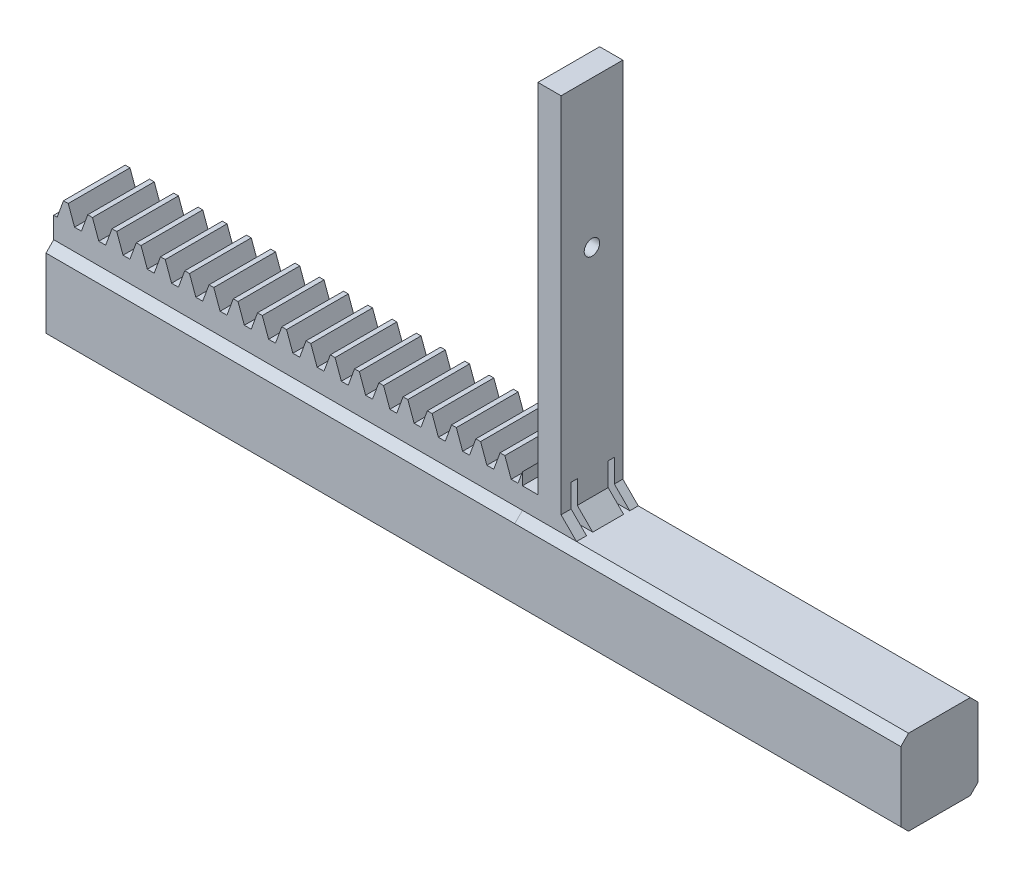
SolidWorks part; units mm, degrees
ref_plane "Front Plane" through (0, 0, 0) normal (0, 0, 1) x (1, 0, 0)
ref_plane "Top Plane" through (0, 0, 0) normal (0, 1, 0) x (1, 0, 0)
ref_plane "Right Plane" through (0, 0, 0) normal (1, 0, 0) x (0, 0, -1)
ref_plane "Plane1" through (0, 0, -3.7928) normal (0, 0, -1) x (-1, 0, 0)
sketch "Sketch1" plane through (0, 0, -3.7928) normal (0, 0, -1) x (-1, 0, 0)
  line L0 (23.517, -6.4086) -> (22.698, -8.6586)
  line L1 (22.698, -8.6586) -> (21.8092, -8.6586)
  line L2 (21.8092, -8.6586) -> (21.2359, -7.0836)
  line L3 (21.2359, -7.0836) -> (21.2359, -12.4086)
  line L4 (21.2359, -12.4086) -> (66.2359, -12.4086)
  line L5 (81.9439, -8.6586) -> (81.9439, -12.4086)
  line L6 (66.6803, -8.6586) -> (65.7915, -8.6586)
  line L7 (65.7915, -8.6586) -> (64.9725, -6.4086)
  line L8 (64.9725, -6.4086) -> (64.3577, -6.4086)
  line L9 (64.3577, -6.4086) -> (63.5387, -8.6586)
  line L10 (63.5387, -8.6586) -> (62.6499, -8.6586)
  line L11 (62.6499, -8.6586) -> (61.8309, -6.4086)
  line L12 (61.8309, -6.4086) -> (61.2161, -6.4086)
  line L13 (61.2161, -6.4086) -> (60.3971, -8.6586)
  line L14 (60.3971, -8.6586) -> (59.5083, -8.6586)
  line L15 (59.5083, -8.6586) -> (58.6893, -6.4086)
  line L16 (58.6893, -6.4086) -> (58.0745, -6.4086)
  line L17 (58.0745, -6.4086) -> (57.2555, -8.6586)
  line L18 (57.2555, -8.6586) -> (56.3667, -8.6586)
  line L19 (56.3667, -8.6586) -> (55.5477, -6.4086)
  line L20 (55.5477, -6.4086) -> (54.9329, -6.4086)
  line L21 (54.9329, -6.4086) -> (54.114, -8.6586)
  line L22 (54.114, -8.6586) -> (53.2251, -8.6586)
  line L23 (53.2251, -8.6586) -> (52.4062, -6.4086)
  line L24 (52.4062, -6.4086) -> (51.7913, -6.4086)
  line L25 (51.7913, -6.4086) -> (50.9724, -8.6586)
  line L26 (50.9724, -8.6586) -> (50.0835, -8.6586)
  line L27 (50.0835, -8.6586) -> (49.2646, -6.4086)
  line L28 (49.2646, -6.4086) -> (48.6497, -6.4086)
  line L29 (48.6497, -6.4086) -> (47.8308, -8.6586)
  line L30 (47.8308, -8.6586) -> (46.9419, -8.6586)
  line L31 (46.9419, -8.6586) -> (46.123, -6.4086)
  line L32 (46.123, -6.4086) -> (45.5081, -6.4086)
  line L33 (45.5081, -6.4086) -> (44.6892, -8.6586)
  line L34 (44.6892, -8.6586) -> (43.8003, -8.6586)
  line L35 (43.8003, -8.6586) -> (42.9814, -6.4086)
  line L36 (42.9814, -6.4086) -> (42.3665, -6.4086)
  line L37 (42.3665, -6.4086) -> (41.5476, -8.6586)
  line L38 (41.5476, -8.6586) -> (40.6587, -8.6586)
  line L39 (40.6587, -8.6586) -> (39.8398, -6.4086)
  line L40 (39.8398, -6.4086) -> (39.2249, -6.4086)
  line L41 (39.2249, -6.4086) -> (38.406, -8.6586)
  line L42 (38.406, -8.6586) -> (37.5171, -8.6586)
  line L43 (37.5171, -8.6586) -> (36.6982, -6.4086)
  line L44 (36.6982, -6.4086) -> (36.0833, -6.4086)
  line L45 (36.0833, -6.4086) -> (35.2644, -8.6586)
  line L46 (35.2644, -8.6586) -> (34.3755, -8.6586)
  line L47 (34.3755, -8.6586) -> (33.5566, -6.4086)
  line L48 (33.5566, -6.4086) -> (32.9417, -6.4086)
  line L49 (32.9417, -6.4086) -> (32.1228, -8.6586)
  line L50 (32.1228, -8.6586) -> (31.2339, -8.6586)
  line L51 (31.2339, -8.6586) -> (30.415, -6.4086)
  line L52 (30.415, -6.4086) -> (29.8001, -6.4086)
  line L53 (29.8001, -6.4086) -> (28.9812, -8.6586)
  line L54 (28.9812, -8.6586) -> (28.0923, -8.6586)
  line L55 (28.0923, -8.6586) -> (27.2734, -6.4086)
  line L56 (27.2734, -6.4086) -> (26.6586, -6.4086)
  line L57 (26.6586, -6.4086) -> (25.8396, -8.6586)
  line L58 (25.8396, -8.6586) -> (24.9508, -8.6586)
  line L59 (24.9508, -8.6586) -> (24.1318, -6.4086)
  line L60 (24.1318, -6.4086) -> (23.517, -6.4086)
  line L61 (81.4994, -8.6586) -> (81.9439, -8.6586)
  line L62 (80.6805, -6.4086) -> (81.4994, -8.6586)
  line L63 (80.0656, -6.4086) -> (80.6805, -6.4086)
  line L64 (79.2467, -8.6586) -> (80.0656, -6.4086)
  line L65 (78.3578, -8.6586) -> (79.2467, -8.6586)
  line L66 (77.5389, -6.4086) -> (78.3578, -8.6586)
  line L67 (76.924, -6.4086) -> (77.5389, -6.4086)
  line L68 (76.1051, -8.6586) -> (76.924, -6.4086)
  line L69 (75.2162, -8.6586) -> (76.1051, -8.6586)
  line L70 (74.3973, -6.4086) -> (75.2162, -8.6586)
  line L71 (73.7824, -6.4086) -> (74.3973, -6.4086)
  line L72 (72.9635, -8.6586) -> (73.7824, -6.4086)
  line L73 (72.0746, -8.6586) -> (72.9635, -8.6586)
  line L74 (71.2557, -6.4086) -> (72.0746, -8.6586)
  line L75 (70.6409, -6.4086) -> (71.2557, -6.4086)
  line L76 (69.8219, -8.6586) -> (70.6409, -6.4086)
  line L77 (68.933, -8.6586) -> (69.8219, -8.6586)
  line L78 (68.1141, -6.4086) -> (68.933, -8.6586)
  line L79 (67.4993, -6.4086) -> (68.1141, -6.4086)
  line L80 (66.6803, -8.6586) -> (67.4993, -6.4086)
  line L81 (66.2359, -12.4086) -> (81.9439, -12.4086)
extrude "Boss-Extrude1" add sketch "Sketch1" against normal blind 8
sketch "Sketch2" plane through (0, -12.4086, 0) normal (0, -1, 0) x (1, 0, 0)
  line L0 (-81.9439, 4.2072) -> (-81.9439, -3.7928) construction
  line L1 (-81.9439, 5.2072) -> (28.7641, 5.2072)
  line L2 (-81.9439, 5.2072) -> (-81.9439, -4.7928)
  line L3 (-81.9439, -4.7928) -> (28.7641, -4.7928)
  line L4 (28.7641, 5.2072) -> (28.7641, -4.7928)
  line L5 (-21.2359, 4.2072) -> (-21.2359, -3.7928) construction
  point P8 (-81.9439, 0.2072)
  dimension "D1" = 10
  dimension "D2" = 50
extrude "Boss-Extrude2" add sketch "Sketch2" along normal blind 10
chamfer "Chamfer1" distance 1 angle 45 1 edges at (-51.5899, -12.4086, 4.2072)
chamfer "Chamfer2" distance 1 angle 45 1 edges at (-51.5899, -12.4086, -3.7928)
sketch "Sketch3" plane through (0, -12.4086, 0) normal (0, 1, 0) x (1, 0, 0)
  line L1 (-21.2359, 3.7928) -> (28.7641, 3.7928)
  line L2 (-21.2359, 3.7928) -> (-21.2359, -4.2072)
  line L3 (-21.2359, -4.2072) -> (28.7641, -4.2072)
  line L4 (28.7641, 3.7928) -> (28.7641, -4.2072)
  line L6 (28.7641, 4.7928) -> (28.7641, -5.2072) construction
  dimension "D1" = 8
extrude "Boss-Extrude3" add sketch "Sketch3" along normal blind 1
chamfer "Chamfer3" distance 1 angle 45 1 edges at (3.7641, -12.4086, 4.2072)
chamfer "Chamfer4" distance 1 angle 45 1 edges at (3.7641, -12.4086, -3.7928)
sketch "Sketch4" plane through (0, -22.4086, 0) normal (0, -1, 0) x (1, 0, 0)
  line L1 (-19.2359, 4.2072) -> (-16.2359, 4.2072)
  line L2 (-19.2359, 4.2072) -> (-19.2359, -3.7928)
  line L3 (-19.2359, -3.7928) -> (-16.2359, -3.7928)
  line L4 (-16.2359, 4.2072) -> (-16.2359, -3.7928)
  line L8 (-81.9439, -4.7928) -> (28.7641, -4.7928) construction
  line L9 (28.7641, -4.7928) -> (28.7641, 5.2072) construction
  dimension "D1" = 48
  dimension "D2" = 3
  dimension "D3" = 8
  dimension "D4" = 1
extrude "Boss-Extrude6" add sketch "Sketch4" against normal blind 60
sketch "Sketch10" plane through (-16.2359, 0, 0) normal (1, 0, 0) x (0, 0, -1)
  line L0 (-4.2072, -11.4086) -> (3.7928, -11.4086) construction
  line L1 (-2.9072, -6.4086) -> (-2.1072, -6.4086)
  line L2 (-2.9072, -6.4086) -> (-2.9072, -11.4086)
  line L3 (-2.9072, -11.4086) -> (-2.1072, -11.4086)
  line L4 (-2.1072, -6.4086) -> (-2.1072, -11.4086)
  line L5 (3.7928, 37.5914) -> (3.7928, -11.4086) construction
  line L6 (1.8928, -6.4086) -> (2.6928, -6.4086)
  line L7 (1.8928, -6.4086) -> (1.8928, -11.4086)
  line L8 (1.8928, -11.4086) -> (2.6928, -11.4086)
  line L9 (2.6928, -6.4086) -> (2.6928, -11.4086)
  dimension "D1" = 0.8
  dimension "D2" = 0.8
  dimension "D3" = 4
  dimension "D4" = 1.1
  dimension "D5" = 5
  dimension "D6" = 5
extrude "Cut-Extrude4" cut sketch "Sketch10" against normal blind 4
sketch "Sketch12" plane through (-19.2359, 0, 0) normal (-1, 0, 0) x (0, 0, 1)
  line L1 (4.2072, 37.5914) -> (-3.7928, 37.5914) construction
  line L2 (4.2072, 37.5914) -> (4.2072, -11.4086) construction
  circle A0 centre (0.2072, 18.5914) radius 1
  dimension "D1" = 2
  dimension "D2" = 19
  dimension "D3" = 4
chamfer "Chamfer7" distance 2 angle 45 3 edges at (-16.2359, -11.4086, 0.1072) (-16.2359, -11.4086, -3.2428) (-16.2359, -11.4086, 3.5572)
extrude "Cut-Extrude5" cut sketch "Sketch12" against normal blind 4
chamfer "Chamfer8" distance 1 angle 45 2 edges at (-26.5899, -22.4086, 5.2072) (-26.5899, -22.4086, -4.7928)
sketch "Sketch13" plane through (0, -11.4086, 0) normal (0, 1, 0) x (1, 0, 0)
  line L1 (-21.2359, 3.7928) -> (-19.2359, 3.7928)
  line L2 (-21.2359, 3.7928) -> (-21.2359, -4.2072)
  line L3 (-21.2359, -4.2072) -> (-19.2359, -4.2072)
  line L4 (-19.2359, 3.7928) -> (-19.2359, -4.2072)
extrude "Boss-Extrude7" add sketch "Sketch13" along normal blind 2.75
